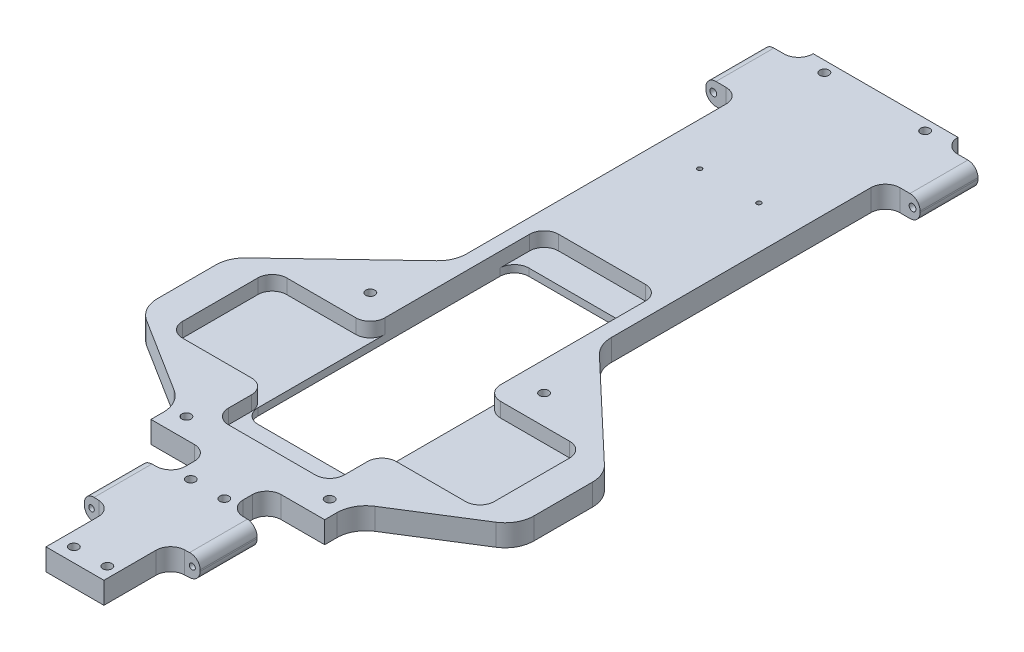
SolidWorks part; units mm, degrees
material "3003-H12"
ref_plane "Front Plane" through (0, 0, 0) normal (0, 0, 1) x (1, 0, 0)
ref_plane "Top Plane" through (0, 0, 0) normal (0, 1, 0) x (1, 0, 0)
ref_plane "Right Plane" through (0, 0, 0) normal (1, 0, 0) x (0, 0, -1)
sketch "Sketch2" plane through (0, 0, 0) normal (0, 1, 0) x (1, 0, 0)
  line L0 (-82.55, 149.86) -> (-31.75, 198.0633)
  line L1 (-12.7, 0) -> (0, 0)
  line L2 (-82.55, 111.76) -> (-82.55, 149.86)
  line L3 (-31.75, 355.5433) -> (31.75, 355.5433)
  line L4 (82.55, 111.76) -> (82.55, 149.86)
  line L5 (-31.75, 198.0633) -> (-31.75, 355.5433)
  line L6 (31.75, 355.5433) -> (31.75, 198.0633)
  line L7 (31.75, 198.0633) -> (82.55, 149.86)
  line L8 (0, 0) -> (0, 485.6184) construction
  line L9 (82.55, 111.76) -> (38.1, 83.82)
  line L10 (38.1, 83.82) -> (38.1, 71.4221)
  line L11 (-38.1, 83.82) -> (-38.1, 71.4221)
  line L12 (-82.55, 111.76) -> (-38.1, 83.82)
  line L13 (0, 0) -> (12.7, 0)
  line L14 (-38.1, 71.4221) -> (-12.7, 71.4221)
  line L15 (-12.7, 71.4221) -> (-12.7, 0)
  line L16 (12.7, 71.4221) -> (12.7, 0)
  line L17 (38.1, 71.4221) -> (12.7, 71.4221)
  dimension "D1" = 76.2
  dimension "D2" = 25.4
  dimension "D3" = 63.5
  dimension "D4" = 157.48
  dimension "D5" = 38.1
  dimension "D6" = 12.3979
  dimension "D7" = 165.1
  dimension "D8" = 111.76
  dimension "D9" = 198.0633
  dimension "D10" = 71.4221
extrude "Chassis" add sketch "Sketch2" against normal blind 9.525
sketch "Sketch4" plane through (0, 0, 0) normal (0, 1, 0) x (1, 0, 0)
  line L0 (0, 0) -> (0, 317.5) construction
  line L2 (25.4, 86.36) -> (-25.4, 86.36)
  line L3 (25.4, 86.36) -> (25.4, 231.14)
  line L4 (25.4, 231.14) -> (-25.4, 231.14)
  line L5 (-25.4, 86.36) -> (-25.4, 231.14)
  line L6 (-12.7, 0) -> (12.7, 0) construction
  line L7 (25.4, 86.36) -> (-25.4, 231.14) construction
  line L8 (25.4, 231.14) -> (-25.4, 86.36) construction
  point P0 (0, 158.75)
  dimension "D1" = 50.8
  dimension "D2" = 144.78
  dimension "D3" = 86.36
extrude "Batt Recess" cut sketch "Sketch4" against normal blind 6.35
sketch "Sketch7" plane through (0, 0, 0) normal (0, 1, 0) x (1, 0, 0)
  line L0 (-25.4, 231.14) -> (-25.4, 86.36) construction
  line L1 (-25.4, 109.22) -> (-68.4, 109.22)
  line L2 (-25.4, 109.22) -> (-25.4, 154.94)
  line L3 (-25.4, 154.94) -> (-68.4, 154.94)
  line L4 (-68.4, 109.22) -> (-68.4, 154.94)
  line L5 (-25.4, 86.36) -> (25.4, 86.36) construction
  dimension "D1" = 43
  dimension "D2" = 45.72
  dimension "D3" = 22.86
extrude "ESC Recess" cut sketch "Sketch7" against normal blind 6.35
mirror "Mirror27" about plane through (0, 0, 0) normal (1, 0, 0) of "ESC Recess"
fillet "Body Fillets" radius 12.7 8 edges at (31.75, -4.7625, -198.0633) (-31.75, -4.7625, -198.0633) (-82.55, -4.7625, -149.86) (-82.55, -4.7625, -111.76) (-38.1, -4.7625, -83.82) (38.1, -4.7625, -83.82) (82.55, -4.7625, -111.76) (82.55, -4.7625, -149.86)
sketch "Sketch8" plane through (0, -6.35, 0) normal (0, 1, 0) x (1, 0, 0)
  line L0 (25.4, 86.36) -> (25.4, 231.14) construction
  line L1 (25.4, 218.14) -> (25.4, 99.36)
  line L2 (-25.4, 86.36) -> (-25.4, 231.14) construction
  line L7 (-25.4, 218.14) -> (25.4, 218.14)
  line L8 (-25.4, 99.36) -> (25.4, 99.36)
  line L9 (-25.4, 218.14) -> (-25.4, 99.36)
  dimension "D1" = 13
  dimension "D2" = 13
extrude "Cut-Extrude1" cut sketch "Sketch8" against normal through all
sketch "Sketch9" plane through (0, 0, 0) normal (0, 1, 0) x (1, 0, 0)
  line L0 (-4.6, 6.1) -> (-4.6, 0) construction
  line L1 (8.1, 8.1) -> (14.1, 8.1) construction
  line L2 (-6.6, 55.4) -> (-14.1, 55.4) construction
  line L3 (-4.6, 57.4) -> (-4.6, 61.5) construction
  line L4 (6.1, 57.4) -> (6.1, 61.5) construction
  line L5 (8.1, 55.4) -> (14.1, 55.4) construction
  line L6 (-12.7, 71.4221) -> (-12.7, 0) construction
  line L7 (-14.1, 0) -> (14.1, 0) construction
  line L8 (-14.1, 0) -> (-14.1, 61.5) construction
  line L9 (-14.1, 61.5) -> (14.1, 61.5) construction
  line L10 (14.1, 0) -> (14.1, 61.5) construction
  line L11 (-6.6, 8.1) -> (-14.1, 8.1) construction
  line L13 (6.1, 6.1) -> (6.1, 0) construction
  line L14 (0, 61.5) -> (0, 0) construction
  line L15 (-14.1, 0) -> (14.1, 0) construction
  line L16 (12.7, 0) -> (12.7, 71.4221) construction
  line L17 (-14.1, 61.5) -> (14.1, 61.5) construction
  line L18 (-12.7, 0) -> (12.7, 0) construction
  line L19 (-12.7, 0) -> (12.7, 0) construction
  circle A0 centre (-6.6, 6.1) radius 2
  circle A1 centre (8.1, 6.1) radius 2
  circle A2 centre (-6.6, 57.4) radius 2
  circle A3 centre (8.1, 57.4) radius 2
  dimension "D1" = 4
  dimension "D2" = 9.5
  dimension "D3" = 28.2
  dimension "D4" = 8
  dimension "D5" = 8.1
  dimension "D6" = 6.1
  dimension "D7" = 9.5
  dimension "D8" = 8
  dimension "D9" = 6.1
  dimension "D11" = 61.5
extrude "Diff Holes" cut sketch "Sketch9" against normal through all
sketch "Sketch10" plane through (0, 0, 0) normal (0, 1, 0) x (1, 0, 0)
  line L0 (-12.7, 71.4221) -> (-12.7, 0) construction
  line L1 (-12.7, 55.0061) -> (-25.4, 54.4981)
  line L2 (-12.7, 55.0061) -> (-12.7, 28.9939)
  line L3 (-12.7, 28.9939) -> (-25.4, 29.5019)
  line L4 (-25.4, 54.4981) -> (-25.4, 29.5019)
  line L8 (-25.4, 42) -> (-12.7, 42) construction
  dimension "D1" = 24.9962
  dimension "D2" = 87.709
  dimension "D3" = 12.7
  dimension "D5" = 42
extrude "Male" add sketch "Sketch10" against normal up to surface (9.525 mm away) up to face at (8.1, -9.525, -59.4)
ref_plane "Plane2" through (0, 0, -42) normal (0, 0, 1) x (1, 0, 0)
sketch "Sketch11" plane through (0, 0, -42) normal (0, 0, 1) x (1, 0, 0)
  line L0 (-22.098, 0) -> (-22.098, -9.525) construction
  line L1 (-25.4, 0) -> (-12.7, 0) construction
  line L2 (-12.7, -9.525) -> (-25.4, -9.525) construction
  line L3 (-25.4, -9.525) -> (-25.4, 0) construction
  circle A0 centre (-22.098, -4.7625) radius 1.27
  dimension "D1" = 2.54
  dimension "D2" = 3.302
extrude "Cut-Extrude3" cut sketch "Sketch11" along normal blind 13.97 and the other way blind 13.97
fillet "Fillet1" radius 4.445 2 edges at (-25.4, -9.525, -42) (-25.4, 0, -42)
fillet "Fillet2" radius 6.35 2 edges at (-12.7, -4.7625, -55.0061) (-12.7, -4.7625, -28.9939)
mirror "Mirror5" about plane through (0, 0, 0) normal (1, 0, 0) of "Male", "Fillet1", "Cut-Extrude3"
fillet "BattRecessFillet" radius 6.35 4 edges
fillet "Inner Fillets" radius 6.35 12 edges at (25.4, -3.175, -231.14) (-25.4, -3.175, -231.14) (-68.4, -3.175, -154.94) (25.4, -3.175, -86.36) (-25.4, -3.175, -86.36) (-68.4, -3.175, -109.22) (68.4, -3.175, -154.94) (68.4, -3.175, -109.22)
sketch "Sketch12" plane through (0, 0, 0) normal (0, 1, 0) x (1, 0, 0)
  line L0 (-31.75, 154.94) -> (-62.05, 154.94) construction
  line L1 (-25.4, 224.79) -> (-25.4, 161.29) construction
  circle A0 centre (-38.1, 167.64) radius 2
  dimension "D1" = 4
  dimension "D2" = 12.7
  dimension "D3" = 12.7
extrude "BatteryMount" cut sketch "Sketch12" against normal through all
mirror "Mirror6" about plane through (0, 0, 0) normal (1, 0, 0) of "BatteryMount"
sketch "Sketch13" plane through (0, 0, 0) normal (0, 1, 0) x (1, 0, 0)
  line L0 (-31.75, 349.0723) -> (-46.99, 349.0723)
  line L1 (-31.75, 355.5433) -> (-31.75, 203.52) construction
  line L2 (-46.99, 349.0723) -> (-46.99, 323.6723)
  line L3 (-46.99, 323.6723) -> (-31.75, 323.6723)
  line L4 (-31.75, 349.0723) -> (-31.75, 323.6723)
  line L5 (-31.75, 336.3723) -> (-59.7537, 336.3723) construction
  line L6 (31.75, 355.5433) -> (-31.75, 355.5433) construction
  dimension "D1" = 25.4
  dimension "D2" = 15.24
  dimension "D3" = 19.171
extrude "Male2" add sketch "Sketch13" against normal up to surface (9.525 mm away) up to face at (-1.0305, -9.525, -105.6114)
fillet "Fillet3" radius 6.35 2 edges at (-31.75, -4.7625, -349.0723) (-31.75, -4.7625, -323.6723)
fillet "Fillet4" radius 4.445 2 edges at (-46.99, -9.525, -336.3723) (-46.99, 0, -336.3723)
sketch "Sketch14" plane through (0, 0, -323.6723) normal (0, 0, 1) x (1, 0, 0)
  line L0 (-46.99, -5.08) -> (-46.99, -4.445) construction
  line L1 (-38.6685, -4.7625) -> (-47.6475, -4.7625) construction
  line L2 (-38.1, 0) -> (-42.545, 0) construction
  line L3 (-42.545, -9.525) -> (-38.1, -9.525) construction
  circle A0 centre (-43.688, -4.7625) radius 1.4958
  dimension "D2" = 2.9916
  dimension "D1" = 3.302
extrude "Cut-Extrude4" cut sketch "Sketch14" against normal through all
mirror "Mirror13" about plane through (0, 0, 0) normal (1, 0, 0) of "Male2"
fillet "Fillet5" radius 4.445 2 edges at (46.99, -9.525, -336.3723) (46.99, 0, -336.3723)
fillet "Fillet6" radius 6.35 2 edges at (31.75, -4.7625, -349.0723) (31.75, -4.7625, -323.6723)
mirror "Mirror21" about plane through (0, 0, 0) normal (1, 0, 0) of "Cut-Extrude4"
sketch "Sketch15" plane through (0, 0, 0) normal (0, 1, 0) x (1, 0, 0)
  line L0 (0, 355.5433) -> (0, 263.7522) construction
  line L1 (31.75, 355.5433) -> (-31.75, 355.5433) construction
  line L2 (13, 286.9633) -> (13, 321.9633) construction
  circle A0 centre (-13, 286.9633) radius 1.016
  circle A1 centre (13, 286.9633) radius 1.016
  dimension "D1" = 2.032
  dimension "D3" = 68.58
  dimension "D2" = 13
  dimension "D4" = 35
sketch "Sketch16" plane through (0, 0, 0) normal (0, 1, 0) x (1, 0, 0)
  line L1 (31.411, 80.2933) -> (38.1, 80.2933) construction
  line L2 (31.411, 80.2933) -> (31.411, 71.4221) construction
  line L3 (31.411, 71.4221) -> (38.1, 71.4221) construction
  line L4 (38.1, 80.2933) -> (38.1, 71.4221) construction
  circle A0 centre (31.411, 80.2933) radius 2
  dimension "D1" = 4
extrude "Cut-Extrude5" cut sketch "Sketch16" against normal through all
mirror "Mirror22" about plane through (0, 0, 0) normal (1, 0, 0) of "Cut-Extrude5"
sketch "Sketch17" plane through (0, 0, 0) normal (0, 1, 0) x (1, 0, 0)
  line L1 (-31.75, 355.5433) -> (-22.098, 355.5433) construction
  line L2 (-31.75, 355.5433) -> (-31.75, 350.7808) construction
  line L3 (-31.75, 350.7808) -> (-22.098, 350.7808) construction
  line L4 (-22.098, 355.5433) -> (-22.098, 350.7808) construction
  circle A0 centre (-22.098, 350.7808) radius 2
  dimension "D1" = 4
extrude "Cut-Extrude6" cut sketch "Sketch17" against normal through all
mirror "Mirror23" about plane through (0, 0, 0) normal (1, 0, 0) of "Cut-Extrude6"
extrude "Cut-Extrude7" cut sketch "Sketch15" against normal through all
fillet "Fillet7" radius 6.35 2 edges at (12.7, -4.7625, -55.0061) (12.7, -4.7625, -28.9939)
fillet "Fillet8" radius 6.35 2 edges at (-12.7, -4.7625, -71.4221) (12.7, -4.7625, -71.4221)
